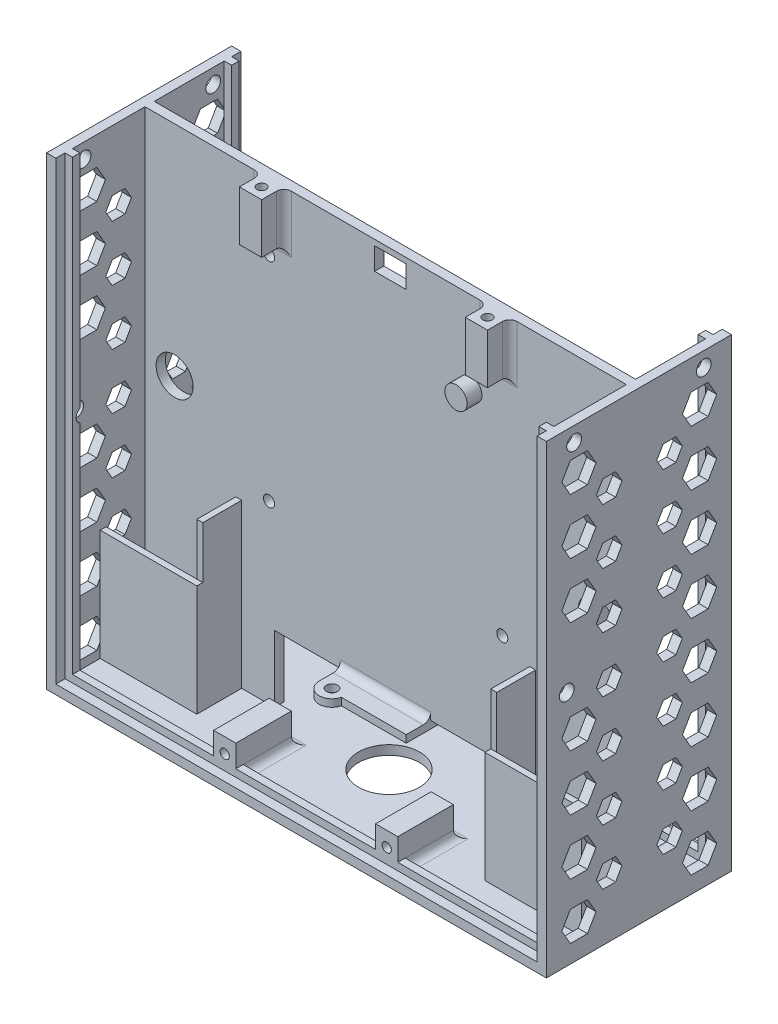
SolidWorks part; units mm, degrees
note: The reader was unsure of these and kept them because the rebuilt part matched: shared geometry of "Sketch1<5>", "Sketch1<6>", "Sketch22<2>".
ref_plane "Front Plane" through (0, 0, 0) normal (0, 0, 1) x (1, 0, 0)
ref_plane "Top Plane" through (0, 0, 0) normal (0, 1, 0) x (1, 0, 0)
ref_plane "Right Plane" through (0, 0, 0) normal (1, 0, 0) x (0, 0, -1)
sketch "Sketch1" plane through (0, 0, 0) normal (0, 0, 1) x (1, 0, 0)
  line L1 (0, 0) -> (130, 0)
  line L3 (0, 123) -> (130, 123)
  line L4 (130, 0) -> (130, 123)
  line L5 (30, 44) -> (100, 44) construction
  line L6 (30, 44) -> (30, 109) construction
  line L7 (30, 109) -> (100, 109) construction
  line L8 (100, 44) -> (100, 109) construction
  line L37 (103.9, 0) -> (103.9, 44)
  line L38 (65, 123) -> (65, 0) construction
  line L40 (105.5, 44) -> (105.5, 0)
  line L53 (105.5, 44) -> (103.9, 44)
  line L55 (0, 123) -> (0, 0)
  line L56 (24.5, 44) -> (24.5, 0)
  line L57 (24.5, 44) -> (26.1, 44)
  line L58 (26.1, 0) -> (26.1, 44)
  line L59 (24.5, 0) -> (26.1, 0)
  line L60 (103.9, 0) -> (105.5, 0)
  line L62 (62, 121.5) -> (70.5, 121.5)
  line L63 (62, 121.5) -> (62, 115.5)
  line L64 (62, 115.5) -> (70.5, 115.5)
  line L65 (70.5, 121.5) -> (70.5, 115.5)
  circle A0 centre (33.523, 105.1) radius 1.5
  circle A1 centre (33.5, 47.5) radius 1.5
  circle A2 centre (96.5, 47.5) radius 1.5
  circle A7 centre (88, 101) radius 3
  circle A8 centre (8, 64) radius 5
  circle A9 centre (122, 64) radius 5
  dimension "D16" = 3
  dimension "D17" = 3.523
  dimension "D18" = 3.9
  dimension "D19" = 3
  dimension "D20" = 3
  dimension "D25" = 44
  dimension "D28" = 5.5
  dimension "D37" = 6
  dimension "D7" = 10
  dimension "D10" = 22
  dimension "D8" = 6
  dimension "D9" = 8.5
  dimension "D27" = 1.5
  dimension "D1" = 130
  dimension "D2" = 123
  dimension "D4" = 14
  dimension "D5" = 65
  dimension "D6" = 70
  dimension "D11" = 45
  dimension "D12" = 30
  dimension "D13" = 44
  dimension "D14" = 1.6
  dimension "D15" = 70
  dimension "D21" = 3.5
  dimension "D22" = 3.5
  dimension "D23" = 3.5
  dimension "D24" = 3.5
  dimension "D26" = 24.5
  dimension "D38" = 12
  dimension "D39" = 8
extrude "Boss-Extrude1" add sketch "Sketch1" along normal blind 2.5
extrude "Boss-Extrude2" add sketch "Sketch1<5>" along normal blind 6.5 contours A7
sketch "Sketch1<5>" plane through (0, 0, 0) normal (0, 0, 1) x (1, 0, 0) same geometry as "Sketch1"
extrude "Boss-Extrude3" add sketch "Sketch1<6>" along normal blind 13
sketch "Sketch1<6>" plane through (0, 0, 0) normal (0, 0, 1) x (1, 0, 0) same geometry as "Sketch1"
sketch "Sketch2" plane through (0, 0, 13) normal (0, 0, 1) x (1, 0, 0)
  line L5 (65, 123) -> (65, 0) construction
  line L17 (65, 123) -> (65, 0) construction
  line L22 (130, 0) -> (130, 123) construction
  line L27 (103.9, 0) -> (130, 0)
  line L28 (103.9, 0) -> (103.9, 30)
  line L29 (103.9, 30) -> (130, 30)
  line L30 (130, 0) -> (130, 30)
  line L31 (0, 123) -> (0, 0) construction
  line L32 (26.1, 0) -> (0, 0)
  line L33 (26.1, 0) -> (26.1, 30)
  line L34 (26.1, 30) -> (0, 30)
  line L35 (0, 0) -> (0, 30)
  dimension "D1" = 30
  dimension "D2" = 30
extrude "Boss-Extrude4" add sketch "Sketch2" along normal blind 1.6
sketch "Sketch3" plane through (0, 0, 0) normal (0, -1, 0) x (1, 0, 0)
  line L0 (105.5, 2.5) -> (130, 2.5) construction
  line L1 (0, -23.4) -> (130, -23.4)
  line L2 (0, -23.4) -> (0, 26.6)
  line L3 (0, 26.6) -> (130, 26.6)
  line L4 (130, -23.4) -> (130, 26.6)
  line L6 (0, -23.4) -> (130, 26.6) construction
  line L7 (130, -23.4) -> (0, 26.6) construction
  circle A0 centre (65, 1.6) radius 8.25
  dimension "D3" = 16.5
  dimension "D1" = 50
  dimension "D2" = 24.1
extrude "Boss-Extrude5" add sketch "Sketch3" along normal blind 2.5
sketch "Sketch4" plane through (0, 0, 2.5) normal (0, 0, 1) x (1, 0, 0)
  line L0 (26.1, 0) -> (56.7992, 0) construction
  line L1 (35, 0) -> (95, 0)
  line L2 (35, 0) -> (35, 18)
  line L3 (35, 18) -> (95, 18)
  line L4 (95, 0) -> (95, 18)
  line L6 (0, 123) -> (0, 0) construction
  dimension "D1" = 18
  dimension "D2" = 35
  dimension "D3" = 60
extrude "Cut-Extrude1" cut sketch "Sketch4" against normal blind 10
sketch "Sketch6" plane through (0, 18, 0) normal (0, -1, 0) x (1, 0, 0)
  line L0 (77.15, 9.109) -> (59.6538, 9.109)
  line L1 (53.85, -7.3) -> (76.15, -7.3) construction
  line L2 (53.85, -7.3) -> (53.85, 12.9) construction
  line L3 (53.85, 12.9) -> (76.15, 12.9) construction
  line L4 (76.15, -7.3) -> (76.15, 12.9) construction
  line L5 (95, 0) -> (35, 0) construction
  line L6 (52.85, -8.3) -> (77.15, -8.3)
  line L7 (52.85, -8.3) -> (52.85, 8.3)
  line L9 (77.15, -8.3) -> (77.15, 9.109)
  circle A0 centre (56.3, 8.3) radius 1.5
  circle A1 centre (73.7, -5.1) radius 1.5
  circle A2 centre (65, 1.6) radius 8.25 construction
  arc A3 (59.6538, 9.109) -> (52.85, 8.3) centre (56.3, 8.3) ccw
  dimension "D9" = 3
  dimension "D13" = 3
  dimension "D1" = 20.2
  dimension "D2" = 22.3
  dimension "D3" = 1
  dimension "D4" = 1
  dimension "D6" = 24.3
  dimension "D7" = 7.3
  dimension "D8" = 4.6
  dimension "D10" = 2.45
  dimension "D11" = 2.2
  dimension "D12" = 2.45
  dimension "D14" = 11.15
extrude "Boss-Extrude6" add sketch "Sketch6" along normal blind 2
sketch "Sketch7" plane through (130, 0, 0) normal (1, 0, 0) x (0, 0, -1)
  line L1 (23.4, -2.5) -> (-26.6, -2.5)
  line L2 (23.4, -2.5) -> (23.4, 123)
  line L3 (23.4, 123) -> (-26.6, 123)
  line L4 (-26.6, -2.5) -> (-26.6, 123)
  dimension "D1" = 50
extrude "Boss-Extrude7" add sketch "Sketch7" along normal blind 2.5
sketch "Sketch8" plane through (0, 0, 0) normal (-1, 0, 0) x (0, 0, 1)
  line L5 (26.6, -2.5) -> (-23.4, -2.5)
  line L6 (26.6, -2.5) -> (26.6, 123)
  line L7 (26.6, 123) -> (-23.4, 123)
  line L8 (-23.4, -2.5) -> (-23.4, 123)
  dimension "D1" = 50
extrude "Boss-Extrude13" add sketch "Sketch8" along normal blind 2.5
sketch "Sketch9" plane through (-2.5, 0, 0) normal (-1, 0, 0) x (0, 0, 1)
  line L0 (-23.4, 123) -> (-23.4, -2.5) construction
  line L1 (26.6, 123) -> (-23.4, 123) construction
  line L5 (-8.65, 153) -> (-8.65, 3) construction
  arc A0 (-8.65, 153) -> (-8.65, 3) centre (-8.65, 78) ccw construction
  dimension "D2" = 150
  dimension "D1" = 14.75
  dimension "D3" = 45
ref_plane "Plane7" through (0, 78, 0) normal (0, 1, 0) x (1, 0, 0)
sketch "Sketch11" plane through (0, 78, 0) normal (0, 1, 0) x (1, 0, 0)
  line L0 (-2.5, 8.65) -> (139.4344, 8.65) construction
  line L1 (65, 23.7811) -> (65, -26.3425) construction
  line L3 (0, -26.6) -> (0, -2.5) construction
  line L4 (115, 23.4) -> (115, -26.6) construction
  line L5 (0, 23.4) -> (130, 23.4) construction
  line L6 (130, -26.6) -> (0, -26.6) construction
  line L7 (15, 23.4) -> (15, -26.6) construction
  line L8 (95, -26.6) -> (95, 23.4) construction
  line L10 (35, -26.6) -> (35, 23.4) construction
  dimension "D1" = 65
  dimension "D2" = 50
  dimension "D3" = 30
sketch "Sketch12" plane through (0, 0, 0) normal (0, 0, -1) x (-1, 0, 0)
  line L0 (-130, 0) -> (-130, 123) construction
  line L1 (-112, 104.9) -> (-109.5, 104.9)
  line L2 (-112, 104.9) -> (-112, 97.4)
  line L3 (-112, 59.9) -> (-109.5, 59.9)
  line L4 (-109.5, 104.9) -> (-109.5, 97.4)
  line L5 (2.5, 78) -> (-139.4344, 78) construction
  line L6 (-112, 97.4) -> (-109.5, 97.4)
  line L7 (-112, 67.4) -> (-109.5, 67.4)
  line L8 (-112, 67.4) -> (-112, 59.9)
  line L9 (-109.5, 67.4) -> (-109.5, 59.9)
  dimension "D1" = 2.5
  dimension "D2" = 18
  dimension "D3" = 45
  dimension "D4" = 18.1
  dimension "D5" = 30
  dimension "D6" = 7.5
extrude "Boss-Extrude14" add sketch "Sketch12" along normal blind 18
sketch "Sketch13" plane through (109.5, 0, 0) normal (-1, 0, 0) x (0, 0, 1)
  line L1 (-18, 97.4) -> (0, 97.4) construction
  line L3 (-18, 67.4) -> (0, 67.4) construction
  line L4 (-18, 59.9) -> (-18, 67.4) construction
  line L5 (-18, 97.4) -> (-18, 104.9) construction
  circle A0 centre (-9, 100.4) radius 1.5
  circle A1 centre (-9, 64.4) radius 1.5
  dimension "D1" = 3
  dimension "D4" = 3
  dimension "D2" = 9
  dimension "D3" = 3
  dimension "D5" = 9
  dimension "D6" = 3
extrude "Cut-Extrude2" cut sketch "Sketch13" against normal blind 2.5
sketch "Sketch14" plane through (109.5, 0, 0) normal (-1, 0, 0) x (0, 0, 1)
  line L0 (-18, 104.9) -> (0, 123)
  line L1 (0, 123) -> (0, 104.9)
  line L2 (0, 104.9) -> (-18, 104.9)
  line L3 (-18, 59.9) -> (0, 41.8)
  line L4 (0, 41.8) -> (0, 59.9)
  line L5 (-18, 59.9) -> (0, 59.9) construction
  line L6 (0, 59.9) -> (-18, 59.9)
  dimension "D1" = 18.1
extrude "Boss-Extrude15" add sketch "Sketch14" against normal blind 2.5
chamfer "Chamfer1" distance 3 angle 45 4 edges at (112, 54.6, 0) (109.5, 54.6, 0) (109.5, 110.2, 0) (112, 110.2, 0)
ref_plane "Plane10" through (65, 0, 0) normal (1, 0, 0) x (0, 0, -1)
mirror "Mirror1" about plane through (65, 0, 0) normal (1, 0, 0) of "Cut-Extrude2", "Chamfer1", "Boss-Extrude15", "Boss-Extrude14"
sketch "Sketch16" plane through (0, 0, -23.4) normal (0, 0, -1) x (-1, 0, 0)
  line L0 (0, 0) -> (-130, 0) construction
  line L1 (-130, 123) -> (-128, 123)
  line L2 (-130, 123) -> (-130, 0)
  line L3 (-130, 0) -> (-128, 0)
  line L4 (-128, 123) -> (-128, 2)
  line L5 (0, 123) -> (-130, 123) construction
  line L6 (-128, 2) -> (-95.5, 2)
  line L8 (-128, 0) -> (-95.5, 0)
  line L9 (0, 2) -> (0, 0)
  line L11 (0, 2) -> (0, 123)
  line L12 (0, 123) -> (-2, 123)
  line L13 (-2, 2) -> (-2, 123)
  line L14 (-95.5, 2) -> (-95.5, 0)
  line L15 (-91.5, 2) -> (-91.5, 0)
  line L16 (-91.5, 2) -> (-38.5, 2)
  line L17 (-91.5, 0) -> (-38.5, 0)
  line L18 (-34.5, 2) -> (-34.5, 0)
  line L19 (-38.5, 2) -> (-38.5, 0)
  line L20 (-34.5, 2) -> (-2, 2)
  line L21 (-34.5, 0) -> (0, 0)
  dimension "D1" = 2
  dimension "D2" = 2
  dimension "D3" = 2
  dimension "D4" = 34.5
  dimension "D5" = 4
  dimension "D6" = 4
  dimension "D7" = 34.5
extrude "Boss-Extrude16" add sketch "Sketch16" against normal blind 2 from offset 2.5 offset against normal yes
sketch "Sketch17" plane through (0, 0, 26.6) normal (0, 0, 1) x (1, 0, 0)
  line L0 (0, 0) -> (130, 0) construction
  line L1 (0, 123) -> (2, 123)
  line L2 (0, 123) -> (0, 0)
  line L3 (0, 0) -> (2, 0)
  line L4 (2, 123) -> (2, 2)
  line L5 (130, 0) -> (130, 123) construction
  line L6 (2, 0) -> (130, 0)
  line L8 (2, 2) -> (128, 2)
  line L9 (130, 0) -> (130, 2)
  line L10 (0, 123) -> (130, 123) construction
  line L12 (130, 2) -> (130, 123)
  line L13 (130, 123) -> (128, 123)
  line L14 (128, 2) -> (128, 123)
  dimension "D1" = 2
  dimension "D2" = 2
  dimension "D3" = 2
extrude "Boss-Extrude17" add sketch "Sketch17" against normal blind 2 from offset 2.5 offset against normal yes
sketch "Sketch18" plane through (-2.5, 0, 0) normal (-1, 0, 0) x (0, 0, 1)
  line L0 (26.6, 123) -> (-23.4, 123) construction
  line L1 (-23.4, 123) -> (-23.4, -2.5) construction
  line L2 (26.6, -2.5) -> (26.6, 123) construction
  circle A0 centre (-15.9, 119) radius 2
  circle A1 centre (19.1, 119) radius 2
  dimension "D1" = 4
  dimension "D2" = 4
  dimension "D3" = 4
  dimension "D4" = 4
  dimension "D5" = 7.5
  dimension "D6" = 7.5
extrude "Cut-Extrude3" cut sketch "Sketch18" against normal through all
sketch "Sketch19" plane through (0, 123, 0) normal (0, 1, 0) x (1, 0, 0)
  line L1 (31.5, -2.5) -> (37.5, -2.5)
  line L2 (31.5, -2.5) -> (31.5, -8.5)
  line L3 (31.5, -8.5) -> (37.5, -8.5)
  line L4 (37.5, -2.5) -> (37.5, -8.5)
  line L7 (-2.5, -26.6) -> (-2.5, 23.4) construction
  line L10 (26.1, -2.5) -> (35, -2.5) construction
  line L11 (65, 23.4) -> (65, -26.6) construction
  line L12 (0, 23.4) -> (130, 23.4) construction
  line L13 (130, -26.6) -> (0, -26.6) construction
  line L14 (98.5, -8.5) -> (92.5, -8.5)
  line L15 (92.5, -2.5) -> (92.5, -8.5)
  line L16 (98.5, -2.5) -> (92.5, -2.5)
  line L17 (98.5, -2.5) -> (98.5, -8.5)
  line L18 (31.5, -2.5) -> (37.5, -8.5) construction
  line L19 (31.5, -8.5) -> (37.5, -2.5) construction
  line L20 (92.5, -2.5) -> (98.5, -8.5) construction
  line L21 (92.5, -8.5) -> (98.5, -2.5) construction
  circle A0 centre (34.5, -5.5) radius 1.25
  circle A1 centre (95.5, -5.5) radius 1.25
  point P18 (34.5, -5.5)
  point P19 (95.5, -5.5)
  dimension "D4" = 2.5
  dimension "D5" = 2.5
  dimension "D1" = 6
  dimension "D2" = 6
  dimension "D3" = 34
extrude "Boss-Extrude18" add sketch "Sketch19" against normal blind 13.5
sketch "Sketch20" plane through (0, 0, 24.1) normal (0, 0, 1) x (1, 0, 0)
  line L0 (130, 0) -> (0, 0) construction
  line L1 (40.125, 0) -> (46.125, 0)
  line L2 (40.125, 0) -> (40.125, 8)
  line L3 (40.125, 8) -> (46.125, 8)
  line L4 (46.125, 0) -> (46.125, 8)
  line L5 (0, 0) -> (130, 0) construction
  line L6 (-2.5, -2.5) -> (-2.5, 123) construction
  line L7 (65, 123) -> (65, 0) construction
  line L8 (65, 123) -> (65, 0) construction
  line L9 (89.875, 8) -> (83.875, 8)
  line L10 (83.875, 0) -> (83.875, 8)
  line L11 (89.875, 0) -> (83.875, 0)
  line L12 (89.875, 0) -> (89.875, 8)
  circle A0 centre (43.125, 4) radius 1.25
  circle A1 centre (86.875, 4) radius 1.25
  dimension "D4" = 2.5
  dimension "D1" = 6
  dimension "D2" = 8
  dimension "D3" = 42.625
  dimension "D5" = 3
  dimension "D6" = 4
extrude "Boss-Extrude19" add sketch "Sketch20" against normal blind 15
fillet "Fillet1" radius 2 6 edges at (95.5, 109.5, 2.5) (98.5, 116.25, 2.5) (92.5, 116.25, 2.5) (37.5, 116.25, 2.5) (31.5, 116.25, 2.5) (34.5, 109.5, 2.5)
fillet "Fillet2" radius 2 12 edges at (65, 18, 2.5) (65, 18, 0) (40.125, 1, 22.1) (46.125, 1, 22.1) (43.125, 0, 9.1) (46.125, 0, 15.6) (40.125, 0, 15.6) (89.875, 1, 22.1) (86.875, 0, 9.1) (89.875, 0, 15.6) (83.875, 1, 22.1) (83.875, 0, 15.6)
sketch "Sketch21" plane through (-2.5, 0, 0) normal (-1, 0, 0) x (0, 0, 1)
  line L0 (-23.4, -2.5) -> (26.6, -2.5) construction
  line L1 (26.6, -2.5) -> (26.6, 123) construction
  circle A0 centre (21.1, 61.5) radius 2
  dimension "D1" = 4
  dimension "D2" = 64
  dimension "D3" = 5.5
extrude "Cut-Extrude4" cut sketch "Sketch21" against normal through all
sketch "Sketch22" plane through (-2.5, 0, 0) normal (-1, 0, 0) x (0, 0, 1)
  line L0 (-23.4, 123) -> (-23.4, -2.5) construction
  line L1 (-12.4718, 107) -> (-10.1624, 111)
  line L2 (-10.1624, 111) -> (-12.4718, 115)
  line L3 (-12.4718, 115) -> (-17.0906, 115)
  line L4 (-17.0906, 115) -> (-19.4, 111)
  line L5 (-19.4, 111) -> (-17.0906, 107)
  line L6 (-17.0906, 107) -> (-12.4718, 107)
  line L7 (26.6, 123) -> (-23.4, 123) construction
  line L14 (20.1194, 107.3269) -> (22.4288, 111.3269)
  line L15 (22.4288, 111.3269) -> (20.1194, 115.3269)
  line L16 (20.1194, 115.3269) -> (15.5006, 115.3269)
  line L17 (15.5006, 115.3269) -> (13.1912, 111.3269)
  line L18 (13.1912, 111.3269) -> (15.5006, 107.3269)
  line L19 (15.5006, 107.3269) -> (20.1194, 107.3269)
  line L26 (20.1194, 92.3269) -> (22.4288, 96.3269)
  line L27 (22.4288, 96.3269) -> (20.1194, 100.3269)
  line L28 (20.1194, 100.3269) -> (15.5006, 100.3269)
  line L29 (15.5006, 100.3269) -> (13.1912, 96.3269)
  line L30 (13.1912, 96.3269) -> (15.5006, 92.3269)
  line L31 (15.5006, 92.3269) -> (20.1194, 92.3269)
  line L38 (20.1194, 77.3269) -> (22.4288, 81.3269)
  line L39 (22.4288, 81.3269) -> (20.1194, 85.3269)
  line L40 (20.1194, 85.3269) -> (15.5006, 85.3269)
  line L41 (15.5006, 85.3269) -> (13.1912, 81.3269)
  line L42 (13.1912, 81.3269) -> (15.5006, 77.3269)
  line L43 (15.5006, 77.3269) -> (20.1194, 77.3269)
  line L62 (20.1194, 47.3269) -> (22.4288, 51.3269)
  line L63 (22.4288, 51.3269) -> (20.1194, 55.3269)
  line L64 (20.1194, 55.3269) -> (15.5006, 55.3269)
  line L65 (15.5006, 55.3269) -> (13.1912, 51.3269)
  line L66 (13.1912, 51.3269) -> (15.5006, 47.3269)
  line L67 (15.5006, 47.3269) -> (20.1194, 47.3269)
  line L74 (20.1194, 32.3269) -> (22.4288, 36.3269)
  line L75 (22.4288, 36.3269) -> (20.1194, 40.3269)
  line L76 (20.1194, 40.3269) -> (15.5006, 40.3269)
  line L77 (15.5006, 40.3269) -> (13.1912, 36.3269)
  line L78 (13.1912, 36.3269) -> (15.5006, 32.3269)
  line L79 (15.5006, 32.3269) -> (20.1194, 32.3269)
  line L86 (20.1194, 17.3269) -> (22.4288, 21.3269)
  line L87 (22.4288, 21.3269) -> (20.1194, 25.3269)
  line L88 (20.1194, 25.3269) -> (15.5006, 25.3269)
  line L89 (15.5006, 25.3269) -> (13.1912, 21.3269)
  line L90 (13.1912, 21.3269) -> (15.5006, 17.3269)
  line L91 (15.5006, 17.3269) -> (20.1194, 17.3269)
  line L98 (20.1194, 2.3269) -> (22.4288, 6.3269)
  line L99 (22.4288, 6.3269) -> (20.1194, 10.3269)
  line L100 (20.1194, 10.3269) -> (15.5006, 10.3269)
  line L101 (15.5006, 10.3269) -> (13.1912, 6.3269)
  line L102 (13.1912, 6.3269) -> (15.5006, 2.3269)
  line L103 (15.5006, 2.3269) -> (20.1194, 2.3269)
  line L104 (-12.4718, 92) -> (-10.1624, 96)
  line L105 (-10.1624, 96) -> (-12.4718, 100)
  line L106 (-12.4718, 100) -> (-17.0906, 100)
  line L107 (-17.0906, 100) -> (-19.4, 96)
  line L108 (-19.4, 96) -> (-17.0906, 92)
  line L109 (-17.0906, 92) -> (-12.4718, 92)
  line L110 (-12.4718, 77) -> (-10.1624, 81)
  line L111 (-10.1624, 81) -> (-12.4718, 85)
  line L112 (-12.4718, 85) -> (-17.0906, 85)
  line L113 (-17.0906, 85) -> (-19.4, 81)
  line L114 (-19.4, 81) -> (-17.0906, 77)
  line L115 (-17.0906, 77) -> (-12.4718, 77)
  line L116 (-12.4718, 62) -> (-10.1624, 66)
  line L117 (-10.1624, 66) -> (-12.4718, 70)
  line L118 (-12.4718, 70) -> (-17.0906, 70)
  line L119 (-17.0906, 70) -> (-19.4, 66)
  line L120 (-19.4, 66) -> (-17.0906, 62)
  line L121 (-17.0906, 62) -> (-12.4718, 62)
  line L122 (-12.4718, 47) -> (-10.1624, 51)
  line L123 (-10.1624, 51) -> (-12.4718, 55)
  line L124 (-12.4718, 55) -> (-17.0906, 55)
  line L125 (-17.0906, 55) -> (-19.4, 51)
  line L126 (-19.4, 51) -> (-17.0906, 47)
  line L127 (-17.0906, 47) -> (-12.4718, 47)
  line L128 (-12.4718, 32) -> (-10.1624, 36)
  line L129 (-10.1624, 36) -> (-12.4718, 40)
  line L130 (-12.4718, 40) -> (-17.0906, 40)
  line L131 (-17.0906, 40) -> (-19.4, 36)
  line L132 (-19.4, 36) -> (-17.0906, 32)
  line L133 (-17.0906, 32) -> (-12.4718, 32)
  line L134 (-12.4718, 17) -> (-10.1624, 21)
  line L135 (-10.1624, 21) -> (-12.4718, 25)
  line L136 (-12.4718, 25) -> (-17.0906, 25)
  line L137 (-17.0906, 25) -> (-19.4, 21)
  line L138 (-19.4, 21) -> (-17.0906, 17)
  line L139 (-17.0906, 17) -> (-12.4718, 17)
  line L140 (-12.4718, 2) -> (-10.1624, 6)
  line L141 (-10.1624, 6) -> (-12.4718, 10)
  line L142 (-12.4718, 10) -> (-17.0906, 10)
  line L143 (-17.0906, 10) -> (-19.4, 6)
  line L144 (-19.4, 6) -> (-17.0906, 2)
  line L145 (-17.0906, 2) -> (-12.4718, 2)
  line L146 (22.4288, 66.3269) -> (20.1194, 70.3269) [skipped]
  line L147 (20.1194, 62.3269) -> (22.4288, 66.3269) [skipped]
  line L148 (20.1194, 70.3269) -> (15.5006, 70.3269) [skipped]
  line L149 (15.5006, 70.3269) -> (13.1912, 66.3269) [skipped]
  line L150 (13.1912, 66.3269) -> (15.5006, 62.3269) [skipped]
  line L151 (15.5006, 62.3269) -> (20.1194, 62.3269) [skipped]
  line L152 (13.0988, 103.6085) -> (11.3668, 106.6085)
  line L159 (-3.2012, 103.6085) -> (-4.9332, 106.6085)
  line L160 (-4.9332, 106.6085) -> (-8.3973, 106.6085)
  line L161 (-8.3973, 106.6085) -> (-10.1294, 103.6085)
  line L162 (-10.1294, 103.6085) -> (-8.3973, 100.6085)
  line L163 (-8.3973, 100.6085) -> (-4.9332, 100.6085)
  line L164 (-4.9332, 100.6085) -> (-3.2012, 103.6085)
  line L165 (11.3668, 106.6085) -> (7.9027, 106.6085)
  line L166 (7.9027, 106.6085) -> (6.1706, 103.6085)
  line L167 (6.1706, 103.6085) -> (7.9027, 100.6085)
  line L168 (7.9027, 100.6085) -> (11.3668, 100.6085)
  line L169 (11.3668, 100.6085) -> (13.0988, 103.6085)
  line L170 (13.0988, 88.6085) -> (11.3668, 91.6085)
  line L171 (11.3668, 91.6085) -> (7.9027, 91.6085)
  line L172 (7.9027, 91.6085) -> (6.1706, 88.6085)
  line L173 (6.1706, 88.6085) -> (7.9027, 85.6085)
  line L174 (7.9027, 85.6085) -> (11.3668, 85.6085)
  line L175 (11.3668, 85.6085) -> (13.0988, 88.6085)
  line L176 (13.0988, 73.6085) -> (11.3668, 76.6085)
  line L177 (11.3668, 76.6085) -> (7.9027, 76.6085)
  line L178 (7.9027, 76.6085) -> (6.1706, 73.6085)
  line L179 (6.1706, 73.6085) -> (7.9027, 70.6085)
  line L180 (7.9027, 70.6085) -> (11.3668, 70.6085)
  line L181 (11.3668, 70.6085) -> (13.0988, 73.6085)
  line L182 (13.0988, 58.6085) -> (11.3668, 61.6085)
  line L183 (11.3668, 61.6085) -> (7.9027, 61.6085)
  line L184 (7.9027, 61.6085) -> (6.1706, 58.6085)
  line L185 (6.1706, 58.6085) -> (7.9027, 55.6085)
  line L186 (7.9027, 55.6085) -> (11.3668, 55.6085)
  line L187 (11.3668, 55.6085) -> (13.0988, 58.6085)
  line L188 (13.0988, 43.6085) -> (11.3668, 46.6085)
  line L189 (11.3668, 46.6085) -> (7.9027, 46.6085)
  line L190 (7.9027, 46.6085) -> (6.1706, 43.6085)
  line L191 (6.1706, 43.6085) -> (7.9027, 40.6085)
  line L192 (7.9027, 40.6085) -> (11.3668, 40.6085)
  line L193 (11.3668, 40.6085) -> (13.0988, 43.6085)
  line L194 (13.0988, 28.6085) -> (11.3668, 31.6085)
  line L195 (11.3668, 31.6085) -> (7.9027, 31.6085)
  line L196 (7.9027, 31.6085) -> (6.1706, 28.6085)
  line L197 (6.1706, 28.6085) -> (7.9027, 25.6085)
  line L198 (7.9027, 25.6085) -> (11.3668, 25.6085)
  line L199 (11.3668, 25.6085) -> (13.0988, 28.6085)
  line L200 (13.0988, 13.6085) -> (11.3668, 16.6085)
  line L201 (11.3668, 16.6085) -> (7.9027, 16.6085)
  line L202 (7.9027, 16.6085) -> (6.1706, 13.6085)
  line L203 (6.1706, 13.6085) -> (7.9027, 10.6085)
  line L204 (7.9027, 10.6085) -> (11.3668, 10.6085)
  line L205 (11.3668, 10.6085) -> (13.0988, 13.6085)
  line L206 (-3.2012, 88.6085) -> (-4.9332, 91.6085)
  line L207 (-4.9332, 91.6085) -> (-8.3973, 91.6085)
  line L208 (-8.3973, 91.6085) -> (-10.1294, 88.6085)
  line L209 (-10.1294, 88.6085) -> (-8.3973, 85.6085)
  line L210 (-8.3973, 85.6085) -> (-4.9332, 85.6085)
  line L211 (-4.9332, 85.6085) -> (-3.2012, 88.6085)
  line L212 (-3.2012, 73.6085) -> (-4.9332, 76.6085)
  line L213 (-4.9332, 76.6085) -> (-8.3973, 76.6085)
  line L214 (-8.3973, 76.6085) -> (-10.1294, 73.6085)
  line L215 (-10.1294, 73.6085) -> (-8.3973, 70.6085)
  line L216 (-8.3973, 70.6085) -> (-4.9332, 70.6085)
  line L217 (-4.9332, 70.6085) -> (-3.2012, 73.6085)
  line L218 (-3.2012, 58.6085) -> (-4.9332, 61.6085)
  line L219 (-4.9332, 61.6085) -> (-8.3973, 61.6085)
  line L220 (-8.3973, 61.6085) -> (-10.1294, 58.6085)
  line L221 (-10.1294, 58.6085) -> (-8.3973, 55.6085)
  line L222 (-8.3973, 55.6085) -> (-4.9332, 55.6085)
  line L223 (-4.9332, 55.6085) -> (-3.2012, 58.6085)
  line L224 (-3.2012, 43.6085) -> (-4.9332, 46.6085)
  line L225 (-4.9332, 46.6085) -> (-8.3973, 46.6085)
  line L226 (-8.3973, 46.6085) -> (-10.1294, 43.6085)
  line L227 (-10.1294, 43.6085) -> (-8.3973, 40.6085)
  line L228 (-8.3973, 40.6085) -> (-4.9332, 40.6085)
  line L229 (-4.9332, 40.6085) -> (-3.2012, 43.6085)
  line L230 (-3.2012, 28.6085) -> (-4.9332, 31.6085)
  line L231 (-4.9332, 31.6085) -> (-8.3973, 31.6085)
  line L232 (-8.3973, 31.6085) -> (-10.1294, 28.6085)
  line L233 (-10.1294, 28.6085) -> (-8.3973, 25.6085)
  line L234 (-8.3973, 25.6085) -> (-4.9332, 25.6085)
  line L235 (-4.9332, 25.6085) -> (-3.2012, 28.6085)
  line L236 (-3.2012, 13.6085) -> (-4.9332, 16.6085)
  line L237 (-4.9332, 16.6085) -> (-8.3973, 16.6085)
  line L238 (-8.3973, 16.6085) -> (-10.1294, 13.6085)
  line L239 (-10.1294, 13.6085) -> (-8.3973, 10.6085)
  line L240 (-8.3973, 10.6085) -> (-4.9332, 10.6085)
  line L241 (-4.9332, 10.6085) -> (-3.2012, 13.6085)
  line L242 (3.8238, 107.1634) -> (6.1332, 111.1634) [skipped]
  line L243 (6.1332, 111.1634) -> (3.8238, 115.1634) [skipped]
  line L244 (3.8238, 115.1634) -> (-0.795, 115.1634) [skipped]
  line L245 (-0.795, 115.1634) -> (-3.1044, 111.1634) [skipped]
  line L246 (-3.1044, 111.1634) -> (-0.795, 107.1634) [skipped]
  line L247 (-0.795, 107.1634) -> (3.8238, 107.1634) [skipped]
  line L248 (3.8238, 92.1634) -> (6.1332, 96.1634) [skipped]
  line L249 (6.1332, 96.1634) -> (3.8238, 100.1634) [skipped]
  line L250 (3.8238, 100.1634) -> (-0.795, 100.1634) [skipped]
  line L251 (-0.795, 100.1634) -> (-3.1044, 96.1634) [skipped]
  line L252 (-3.1044, 96.1634) -> (-0.795, 92.1634) [skipped]
  line L253 (-0.795, 92.1634) -> (3.8238, 92.1634) [skipped]
  line L254 (3.8238, 77.1634) -> (6.1332, 81.1634) [skipped]
  line L255 (6.1332, 81.1634) -> (3.8238, 85.1634) [skipped]
  line L256 (3.8238, 85.1634) -> (-0.795, 85.1634) [skipped]
  line L257 (-0.795, 85.1634) -> (-3.1044, 81.1634) [skipped]
  line L258 (-3.1044, 81.1634) -> (-0.795, 77.1634) [skipped]
  line L259 (-0.795, 77.1634) -> (3.8238, 77.1634) [skipped]
  line L260 (3.8238, 62.1634) -> (6.1332, 66.1634) [skipped]
  line L261 (6.1332, 66.1634) -> (3.8238, 70.1634) [skipped]
  line L262 (3.8238, 70.1634) -> (-0.795, 70.1634) [skipped]
  line L263 (-0.795, 70.1634) -> (-3.1044, 66.1634) [skipped]
  line L264 (-3.1044, 66.1634) -> (-0.795, 62.1634) [skipped]
  line L265 (-0.795, 62.1634) -> (3.8238, 62.1634) [skipped]
  line L266 (3.8238, 47.1634) -> (6.1332, 51.1634) [skipped]
  line L267 (6.1332, 51.1634) -> (3.8238, 55.1634) [skipped]
  line L268 (3.8238, 55.1634) -> (-0.795, 55.1634) [skipped]
  line L269 (-0.795, 55.1634) -> (-3.1044, 51.1634) [skipped]
  line L270 (-3.1044, 51.1634) -> (-0.795, 47.1634) [skipped]
  line L271 (-0.795, 47.1634) -> (3.8238, 47.1634) [skipped]
  line L272 (3.8238, 32.1634) -> (6.1332, 36.1634) [skipped]
  line L273 (6.1332, 36.1634) -> (3.8238, 40.1634) [skipped]
  line L274 (3.8238, 40.1634) -> (-0.795, 40.1634) [skipped]
  line L275 (-0.795, 40.1634) -> (-3.1044, 36.1634) [skipped]
  line L276 (-3.1044, 36.1634) -> (-0.795, 32.1634) [skipped]
  line L277 (-0.795, 32.1634) -> (3.8238, 32.1634) [skipped]
  line L278 (3.8238, 17.1634) -> (6.1332, 21.1634) [skipped]
  line L279 (6.1332, 21.1634) -> (3.8238, 25.1634) [skipped]
  line L280 (3.8238, 25.1634) -> (-0.795, 25.1634) [skipped]
  line L281 (-0.795, 25.1634) -> (-3.1044, 21.1634) [skipped]
  line L282 (-3.1044, 21.1634) -> (-0.795, 17.1634) [skipped]
  line L283 (-0.795, 17.1634) -> (3.8238, 17.1634) [skipped]
  line L284 (3.8238, 2.1634) -> (6.1332, 6.1634) [skipped]
  line L285 (6.1332, 6.1634) -> (3.8238, 10.1634) [skipped]
  line L286 (3.8238, 10.1634) -> (-0.795, 10.1634) [skipped]
  line L287 (-0.795, 10.1634) -> (-3.1044, 6.1634) [skipped]
  line L288 (-3.1044, 6.1634) -> (-0.795, 2.1634) [skipped]
  line L289 (-0.795, 2.1634) -> (3.8238, 2.1634) [skipped]
  circle A0 centre (-14.7812, 111) radius 4 construction
  circle A1 centre (-6.6653, 103.6085) radius 3 construction
  dimension "D1" = 8
  dimension "D6" = 6
  dimension "D2" = 4
  dimension "D3" = 8
  dimension "D4" = 3
  dimension "D5" = 8
  dimension "D7" = 2
  dimension "D8" = 7
extrude "Cut-Extrude5" cut sketch "Sketch22" against normal blind 2.5
extrude "Cut-Extrude6" cut sketch "Sketch22<2>" against normal blind 2.5 from surface at -132.5
sketch "Sketch22<2>" plane through (-2.5, 0, 0) normal (-1, 0, 0) x (0, 0, 1) same geometry as "Sketch22"
